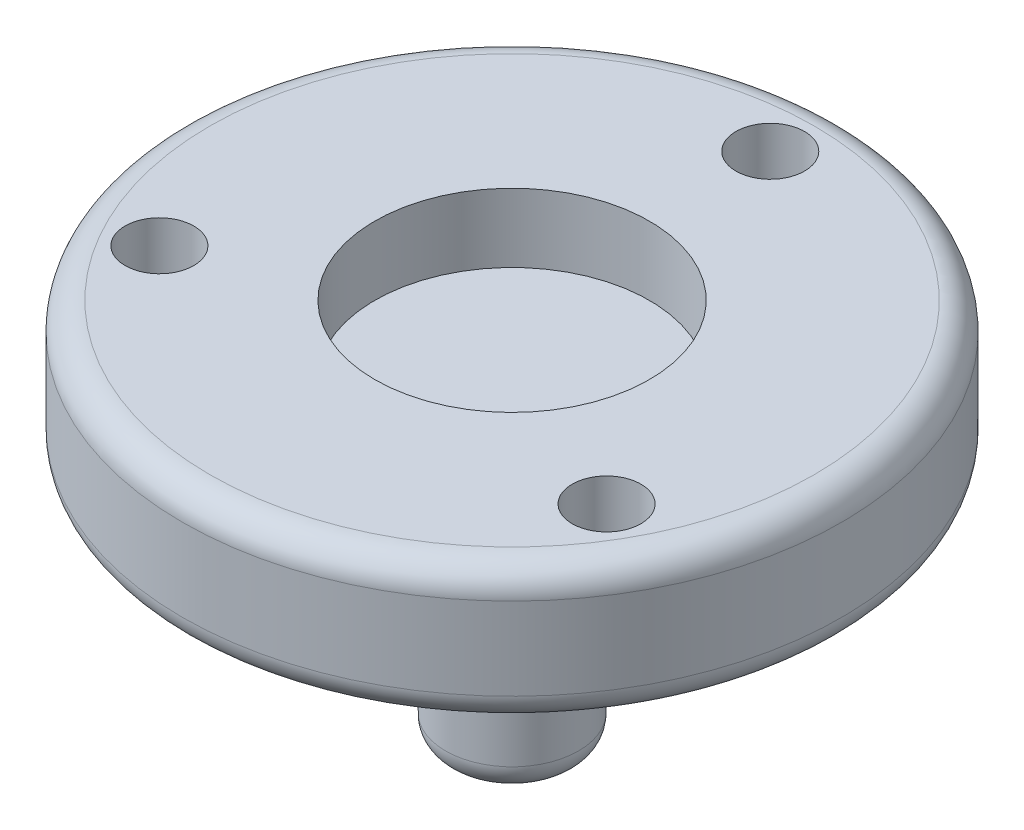
SolidWorks part; units mm, degrees
ref_plane "Front Plane" through (0, 0, 0) normal (0, 0, 1) x (1, 0, 0)
ref_plane "Top Plane" through (0, 0, 0) normal (0, 1, 0) x (1, 0, 0)
ref_plane "Right Plane" through (0, 0, 0) normal (1, 0, 0) x (0, 0, -1)
sketch "Sketch1" plane through (0, 0, 0) normal (0, 1, 0) x (1, 0, 0)
  circle A0 centre (0, 0) radius 15.24
extrude "Boss-Extrude1" add sketch "Sketch1" along normal blind 6.35
sketch "Sketch2" plane through (0, 6.35, 0) normal (0, 1, 0) x (1, 0, 0)
  circle A0 centre (0, 0) radius 6.35
extrude "Cut-Extrude1" cut sketch "Sketch2" against normal blind 3.175
sketch "Sketch3" plane through (0, 0, 0) normal (0, -1, 0) x (1, 0, 0)
  circle A0 centre (0, 0) radius 3.0734
fillet "Fillet4" radius 1.27 1 edges at (0, 6.35, 15.24)
extrude "Boss-Extrude3" add sketch "Sketch3" along normal blind 11.43 contours A0
fillet "Fillet5" radius 1.27 3 edges at (0, -11.43, -3.0734) (0, 0, 15.24) (0, 0, -3.0734)
sketch "Sketch4" plane through (0, 6.35, 0) normal (0, 1, 0) x (1, 0, 0)
  line L0 (0, 0) -> (0, 13.97) construction
  circle A0 centre (0, 0) radius 13.97 construction
  circle A1 centre (0, 0) radius 11.938 construction
  circle A2 centre (0, 11.938) radius 1.5875
extrude "Cut-Extrude2" cut sketch "Sketch4" against normal blind 2.54
ref_axis "Axis1" through (0, 3.175, 0) along (0, 1, 0)
pattern_circular "CirPattern1" count 3 every 120 about axis through (0, 3.175, 0) along (0, 1, 0) of "Cut-Extrude2"
